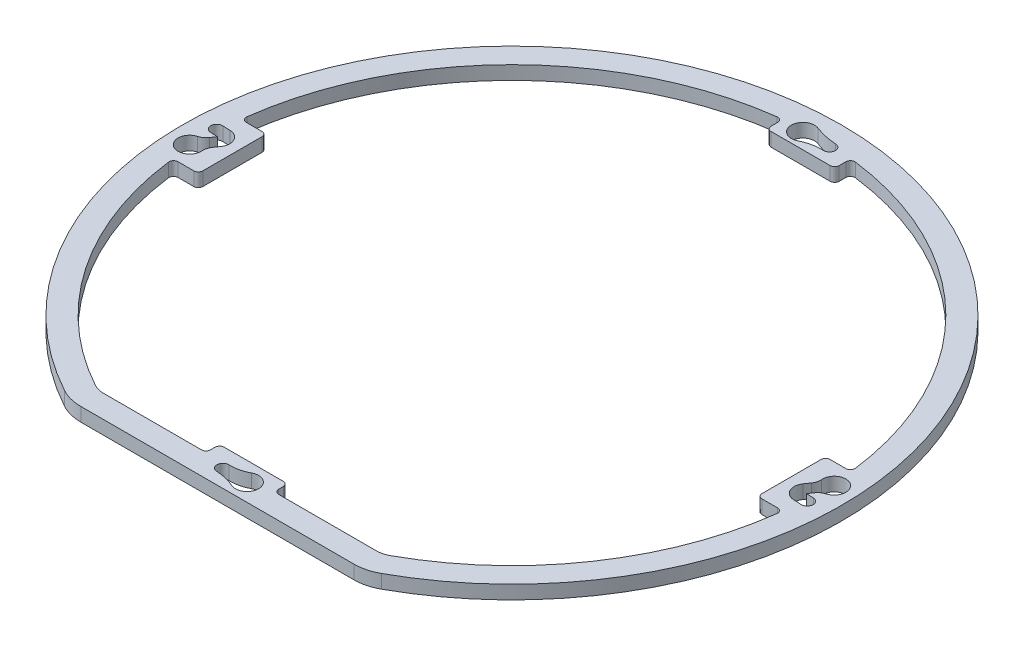
SolidWorks part; units mm, degrees
material "ABS"
ref_plane "Front Plane" through (0, 0, 0) normal (0, 0, 1) x (1, 0, 0)
ref_plane "Top Plane" through (0, 0, 0) normal (0, 1, 0) x (1, 0, 0)
ref_plane "Right Plane" through (0, 0, 0) normal (1, 0, 0) x (0, 0, -1)
sketch "Sketch1" plane through (0, 0, 0) normal (0, 1, 0) x (1, 0, 0)
  line L0 (-30.03, -64.8129) -> (30.03, -64.8129)
  line L1 (0, -85) -> (0, 0) construction
  line L2 (0, -85) -> (32.4891, -64.8129) construction
  line L3 (-30.03, -59.8129) -> (30.03, -59.8129)
  arc A0 (34.8348, -63.5829) -> (-34.8348, -63.5829) centre (0, 0) ccw
  circle A1 centre (0, -85) radius 38.25 construction
  arc A2 (30.03, -64.8129) -> (34.8348, -63.5829) centre (30.03, -54.8129) ccw
  arc A3 (-30.03, -64.8129) -> (-34.8348, -63.5829) centre (-30.03, -54.8129) cw
  arc A4 (32.4324, -59.1979) -> (-32.4324, -59.1979) centre (0, 0) ccw
  arc A5 (-30.03, -59.8129) -> (-32.4324, -59.1979) centre (-30.03, -54.8129) cw
  arc A6 (30.03, -59.8129) -> (32.4324, -59.1979) centre (30.03, -54.8129) ccw
  dimension "D1" = 145
  dimension "D2" = 76.5
  dimension "D4" = 10
  dimension "D3" = 85
  dimension "D5" = 5
extrude "Boss-Extrude1" add sketch "Sketch1" along normal blind 3
sketch "Sketch2" plane through (0, 3, 0) normal (0, 1, 0) x (1, 0, 0)
  line L0 (-30.03, -59.8129) -> (30.03, -59.8129) construction
  line L1 (7.5, -59.8129) -> (-7.5, -59.8129)
  line L2 (7.5, -59.8129) -> (7.5, -56.8129)
  line L3 (7.5, -56.8129) -> (-7.5, -56.8129)
  line L4 (-7.5, -59.8129) -> (-7.5, -56.8129)
  line L5 (-30.03, -64.8129) -> (30.03, -64.8129) construction
  line L6 (-61.5, -7.5) -> (-67.5, -7.5)
  line L7 (-61.5, -7.5) -> (-61.5, 7.5)
  line L8 (-61.5, 7.5) -> (-67.5, 7.5)
  line L9 (-67.5, -7.5) -> (-67.5, 7.5)
  line L10 (61.5, -7.5) -> (67.5, -7.5)
  line L11 (61.5, -7.5) -> (61.5, 7.5)
  line L12 (61.5, 7.5) -> (67.5, 7.5)
  line L13 (67.5, -7.5) -> (67.5, 7.5)
  line L14 (7.5, 67.5) -> (-7.5, 67.5)
  line L15 (7.5, 67.5) -> (7.5, 63.5)
  line L16 (7.5, 63.5) -> (-7.5, 63.5)
  line L17 (-7.5, 67.5) -> (-7.5, 63.5)
  arc A0 (32.4324, -59.1979) -> (-32.4324, -59.1979) centre (0, 0) ccw construction
  point P17 (-67.5, 0)
  point P18 (67.5, 0)
  point P20 (0, -56.8129)
  point P26 (0, 67.5)
  dimension "D4" = 4
  dimension "D1" = 15
  dimension "D2" = 8
  dimension "D3" = 15
  dimension "D5" = 6
extrude "Boss-Extrude2" add sketch "Sketch2" against normal up to surface (3 mm away) up to face at (0, 0, 30.3285)
sketch "Sketch3" plane through (0, 3, 0) normal (0, 1, 0) x (1, 0, 0)
  line L0 (0, 0) -> (2.6608, -60.9419) construction
  line L1 (0, 0) -> (-2.6608, -60.9419) construction
  line L2 (0, 0) -> (0, -64.8129) construction
  line L3 (-30.03, -64.8129) -> (30.03, -64.8129) construction
  line L4 (0, 0) -> (0, 72.5) construction
  line L5 (0, 0) -> (2.9225, 66.9362) construction
  line L6 (0, 0) -> (-2.9225, 66.9362) construction
  arc A0 (1.6164, -63.2683) -> (1.438, -58.7042) centre (2.6608, -60.9419) ccw
  arc A1 (-2.6041, -59.6432) -> (-2.7175, -62.2407) centre (-2.6608, -60.9419) ccw
  arc A2 (-2.6041, -59.6432) -> (1.438, -58.7042) centre (-2.2671, -51.9241) ccw
  arc A3 (1.6164, -63.2683) -> (-2.7175, -62.2407) centre (-3.2341, -74.0728) ccw
  arc A4 (34.8348, -63.5829) -> (-34.8348, -63.5829) centre (0, 0) ccw construction
  arc A5 (2.8658, 65.6375) -> (2.9792, 68.235) centre (2.9225, 66.9362) ccw
  arc A6 (-1.9738, 69.3032) -> (-1.7885, 64.6522) centre (-2.9225, 66.9362) ccw
  arc A7 (-1.9738, 69.3032) -> (2.9792, 68.235) centre (3.6371, 83.3026) ccw
  arc A8 (2.8658, 65.6375) -> (-1.7885, 64.6522) centre (2.45, 56.1152) ccw
  point P23 (0, 0)
  dimension "D1" = 2.6
  dimension "D2" = 5.1
  dimension "D6" = 5.1
  dimension "D7" = 2.6
  dimension "D3" = 5
  dimension "D4" = 2.5
  dimension "D5" = 61
  dimension "D8" = 2.5
  dimension "D9" = 5
  dimension "D10" = 67
extrude "Cut-Extrude1" cut sketch "Sketch3" against normal through all
sketch "Sketch4" plane through (0, 3, 0) normal (0, 1, 0) x (1, 0, 0)
  line L0 (0, 0) -> (-72.5, 0) construction
  line L1 (0, 0) -> (-67.9353, -2.9661) construction
  line L2 (0, 0) -> (-67.9353, 2.9661) construction
  line L3 (-67.9353, -2.9661) -> (-63.9391, 2.7916) construction
  line L4 (-67.992, 1.6674) -> (-66.4106, 1.5983)
  line L5 (-67.1396, 0.548) -> (-66.4106, 1.5983)
  line L6 (-69.0443, -2.1964) -> (-65.0481, 3.5614) construction
  line L7 (-64.9215, -0.9914) -> (-64.1565, 0.1107)
  line L8 (-67.8786, 4.2649) -> (-66.1791, 4.1907)
  line L9 (67.992, -1.6674) -> (66.4106, -1.5983)
  line L10 (67.1396, -0.548) -> (66.4106, -1.5983)
  line L11 (64.9215, 0.9914) -> (64.1565, -0.1107)
  line L12 (67.8786, -4.2649) -> (66.1791, -4.1907)
  line L13 (0, 0) -> (72.5, 0) construction
  line L14 (0, 0) -> (67.9353, 2.9661) construction
  line L15 (0, 0) -> (67.9353, -2.9661) construction
  line L16 (67.9353, 2.9661) -> (63.9391, -2.7916) construction
  arc A0 (34.8348, -63.5829) -> (-34.8348, -63.5829) centre (0, 0) ccw construction
  arc A1 (-67.8786, 4.2649) -> (-67.992, 1.6674) centre (-67.9353, 2.9661) ccw
  arc A2 (-68.6262, -0.5115) -> (-65.3941, -2.7547) centre (-67.9353, -2.9661) ccw
  arc A3 (-66.1791, 4.1907) -> (-64.1565, 0.1107) centre (-66.2925, 1.5932) cw
  arc A4 (-67.1396, 0.548) -> (-68.6262, -0.5115) centre (-69.3577, 2.0875) cw
  arc A5 (-64.9215, -0.9914) -> (-65.3941, -2.7547) centre (-62.7033, -2.5309) ccw
  arc A6 (67.8786, -4.2649) -> (67.992, -1.6674) centre (67.9353, -2.9661) ccw
  arc A7 (68.6262, 0.5115) -> (65.3941, 2.7547) centre (67.9353, 2.9661) ccw
  arc A8 (66.1791, -4.1907) -> (64.1565, -0.1107) centre (66.2925, -1.5932) cw
  arc A9 (67.1396, -0.548) -> (68.6262, 0.5115) centre (69.3577, -2.0875) cw
  arc A10 (64.9215, 0.9914) -> (65.3941, 2.7547) centre (62.7033, 2.5309) ccw
  point P42 (0, 0)
  dimension "D5" = 5.1
  dimension "D6" = 2.6
  dimension "D9" = 2.7
  dimension "D1" = 68
  dimension "D2" = 5
  dimension "D3" = 2.5
  dimension "D4" = 4
  dimension "D7" = 1.35
  dimension "D8" = 1.35
  dimension "D10" = 2
extrude "Cut-Extrude2" cut sketch "Sketch4" against normal through all
fillet "Fillet1" radius 1 16 edges at (61.5, 1.5, -7.5) (67.082, 1.5, -7.5) (61.5, 1.5, 7.5) (67.082, 1.5, 7.5) (-7.5, 1.5, -63.5) (-7.5, 1.5, -67.082) (7.5, 1.5, -63.5) (7.5, 1.5, -67.082) (-67.082, 1.5, -7.5) (-61.5, 1.5, -7.5) (-61.5, 1.5, 7.5) (-67.082, 1.5, 7.5) (-7.5, 1.5, 59.8129) (-7.5, 1.5, 56.8129) (7.5, 1.5, 56.8129) (7.5, 1.5, 59.8129)
equation "\"smallPulleyTeeth\"= 30"
equation "\"largePulleyTeeth\"= 30"
equation "\"eighthThick\"= 3.0mm"
equation "\"sixteenthThick\"= 1.7mm"
equation "\"quarterThick\"=6.0mm"
equation "\"OD\"= 145mm"
equation "\"puckAngle\"= 60.5deg"
equation "\"puckDiam\"= 76.5mm"
equation "\"axlePress\"= 5.9mm"
equation "\"press\"= 0.2mm"
equation "\"wheelClear\"= 0.3mm"
equation "\"10-32clear\"= 4.8mm"
equation "\"6-32clear\"= 3.3mm"
equation "\"8-32clear\"= 4.0mm"
equation "\"4-40clear\"= 3.0mm"
equation "\"wheelHeight\"= 22mm"
equation "\"wheelWell\"= 65mm"
equation "\"D1@Sketch1\"=\"OD\""
equation "\"D1@Boss-Extrude1\"=\"eighthThick\""
equation "\"D2@Sketch1\"=\"puckDiam\""
equation "\"puckDist\"= 85mm"
equation "\"scoopFillet\"= 5mm"
equation "\"10-32tap\"= 4.45mm"
equation "\"ledSmall\"= 3.1mm"
equation "\"ledLarge\"= 4.2mm"
equation "\"ledLength\"= 4.2mm"
equation "\"D3@Sketch1\"=\"puckDist\""
